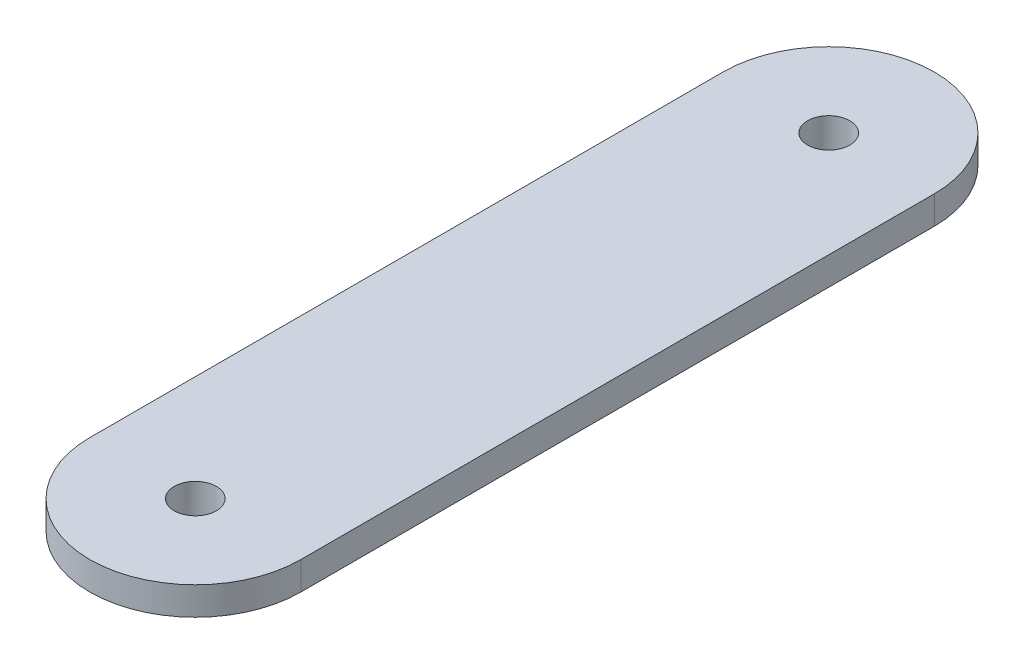
SolidWorks part; units mm, degrees
ref_plane "Front Plane" through (0, 0, 0) normal (0, 0, 1) x (1, 0, 0)
ref_plane "Top Plane" through (0, 0, 0) normal (0, 1, 0) x (1, 0, 0)
ref_plane "Right Plane" through (0, 0, 0) normal (1, 0, 0) x (0, 0, -1)
sketch "Sketch1" plane through (0, 0, 0) normal (0, 1, 0) x (1, 0, 0)
  line L0 (0, 22.5) -> (0, -22.5) construction
  line L1 (7.5, 22.5) -> (7.5, -22.5)
  line L2 (-7.5, 22.5) -> (-7.5, -22.5)
  arc A0 (7.5, 22.5) -> (-7.5, 22.5) centre (0, 22.5) ccw
  arc A1 (-7.5, -22.5) -> (7.5, -22.5) centre (0, -22.5) ccw
  point P3 (0, 0)
  dimension "D1" = 45
  dimension "D2" = 15
extrude "Boss-Extrude1" add sketch "Sketch1" along normal blind 2
sketch "Sketch2" plane through (0, 2, 0) normal (0, 1, 0) x (1, 0, 0)
  circle A0 centre (0, 22.5) radius 1.5
  circle A1 centre (0, -22.5) radius 1.5
  dimension "D1" = 3
  dimension "D2" = 3
extrude "Cut-Extrude1" cut sketch "Sketch2" against normal through all
sketch "Sketch3" plane through (0, 0, 0) normal (0, -1, 0) x (1, 0, 0)
  line L0 (0, 0) -> (22.2854, 0) construction
  circle A0 centre (0, 22.5) radius 1.5
  circle A1 centre (0, 22.5) radius 2.25
  circle A2 centre (0, -22.5) radius 1.5
  circle A3 centre (0, -22.5) radius 2.25
  dimension "D1" = 4.5
  dimension "D2" = 3
extrude "Boss-Extrude2" add sketch "Sketch3" along normal blind 0.5
fillet "Fillet1" radius 5 2 edges at (0, 0, -20.25) (0, 0, 24.75)
ref_axis "Axis1" through (0, -0.5, 22.5) along (0, 1, 0)
ref_axis "Axis2" through (0, -0.5, -22.5) along (0, 1, 0)
